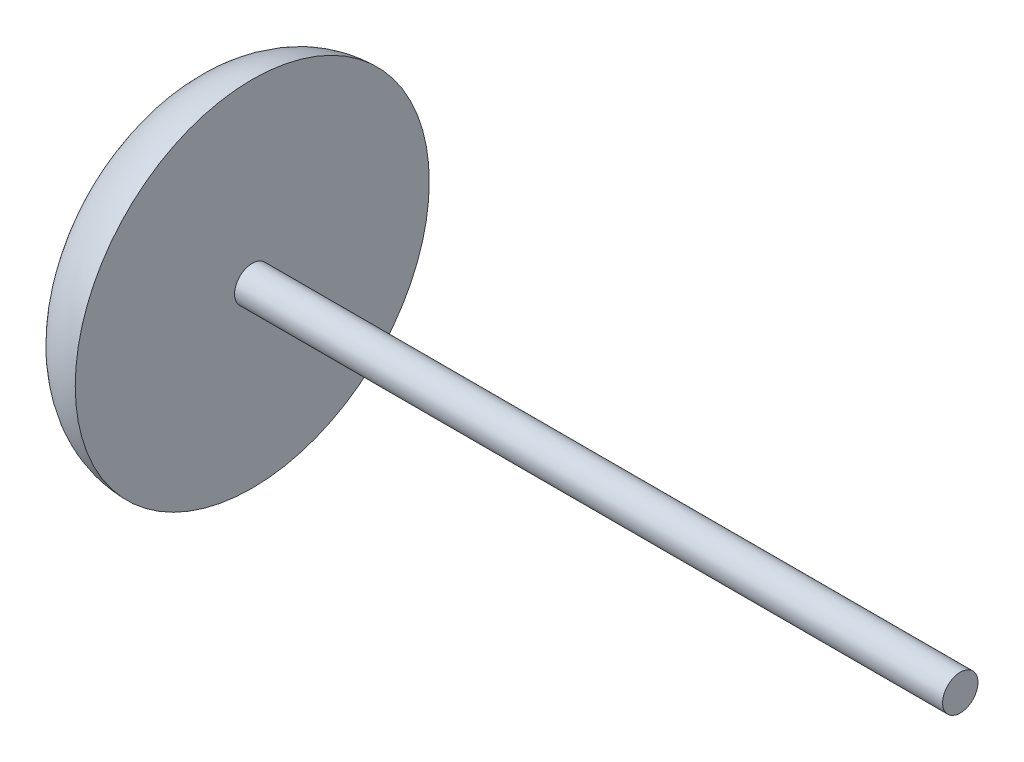
SolidWorks part; units mm, degrees
ref_plane "Ön Düzlem" through (0, 0, 0) normal (0, 0, 1) x (1, 0, 0)
ref_plane "Üst Düzlem" through (0, 0, 0) normal (0, 1, 0) x (1, 0, 0)
ref_plane "Sağ Düzlem" through (0, 0, 0) normal (1, 0, 0) x (0, 0, -1)
sketch "Sketch1" plane through (0, 0, 0) normal (1, 0, 0) x (0, 0, -1)
  circle A0 centre (0, 0) radius 25
extrude "Boss-Extrude1" add sketch "Sketch1" along normal blind 110
sketch "Sketch2" plane through (110, 0, 0) normal (1, 0, 0) x (0, 0, -1)
  circle A0 centre (0, 0) radius 2.5
  circle A1 centre (0, 0) radius 25
extrude "Cut-Extrude1" cut sketch "Sketch2" against normal blind 100
fillet "Fillet1" radius 10 1 edges at (0, 0, -25)
